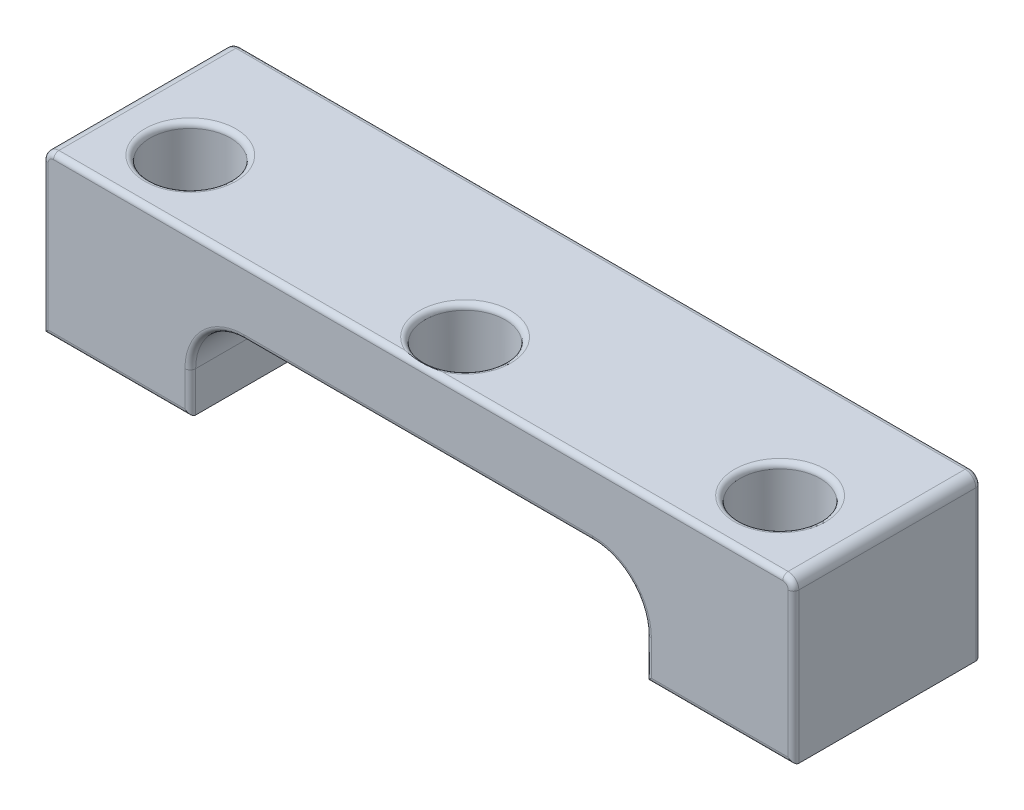
SolidWorks part; units mm, degrees
ref_plane "Ön Düzlem" through (0, 0, 0) normal (0, 0, 1) x (1, 0, 0)
ref_plane "Üst Düzlem" through (0, 0, 0) normal (0, 1, 0) x (1, 0, 0)
ref_plane "Sağ Düzlem" through (0, 0, 0) normal (1, 0, 0) x (0, 0, -1)
sketch "Sketch1" plane through (0, 0, 0) normal (0, 0, 1) x (1, 0, 0)
  line L0 (-14, 0) -> (-14, 6)
  line L1 (-14, 6) -> (14, 6)
  line L2 (14, 6) -> (14, 0)
  line L3 (0, 0) -> (0, 6) construction
  line L4 (-14, 0) -> (-8.5, 0)
  line L5 (-8.5, 0) -> (-8.5, 3.5)
  line L6 (-8.5, 3.5) -> (8.5, 3.5)
  line L7 (8.5, 3.5) -> (8.5, 0)
  line L8 (8.5, 0) -> (14, 0)
  dimension "D1" = 28
  dimension "D2" = 6
  dimension "D3" = 5.5
  dimension "D4" = 3.5
extrude "Boss-Extrude1" add sketch "Sketch1" along normal mid plane 7
sketch "Sketch2" plane through (0, 6, 0) normal (0, 1, 0) x (1, 0, 0)
  line L3 (0, 0) -> (0, -3.5) construction
  line L4 (14, -3.5) -> (-14, -3.5) construction
  circle A0 centre (11, -1) radius 1.5
  circle A1 centre (-11, -1) radius 1.5
  circle A2 centre (0, -1.75) radius 1.5
  dimension "D1" = 3
  dimension "D2" = 11
  dimension "D3" = 2.5
extrude "Cut-Extrude1" cut sketch "Sketch2" against normal through all
fillet "Fillet1" radius 2 2 edges at (8.5, 3.5, 0) (-8.5, 3.5, 0)
fillet "Fillet2" radius 0.4 2 edges at (14, 6, 0) (-14, 6, 0)
fillet "Fillet3" radius 0.2 27 edges at (11.25, 0, 3.5) (8.5, 0.75, 3.5) (7.9142, 2.9142, 3.5) (0, 3.5, 3.5) (-7.9142, 2.9142, 3.5) (-8.5, 0.75, 3.5) (-11.25, 0, 3.5) (-14, 2.8, 3.5) (-13.8828, 5.8828, 3.5) (0, 6, 3.5) (13.8828, 5.8828, 3.5) (14, 2.8, 3.5) (-13.8828, 5.8828, -3.5) (-14, 2.8, -3.5) (-11.25, 0, -3.5) (-8.5, 0.75, -3.5) (-7.9142, 2.9142, -3.5) (0, 3.5, -3.5) (7.9142, 2.9142, -3.5) (8.5, 0.75, -3.5) (11.25, 0, -3.5) (14, 2.8, -3.5) (13.8828, 5.8828, -3.5) (0, 6, -3.5) (-11, 6, -0.5) (11, 6, 2.5) (0, 6, 3.25)
ref_plane "Plane1" through (0, 3.5, 0) normal (0, -1, 0) x (-1, 0, 0)
ref_axis "Axis1" through (0, 3.5, -3.63) along (0, 0, 1)
